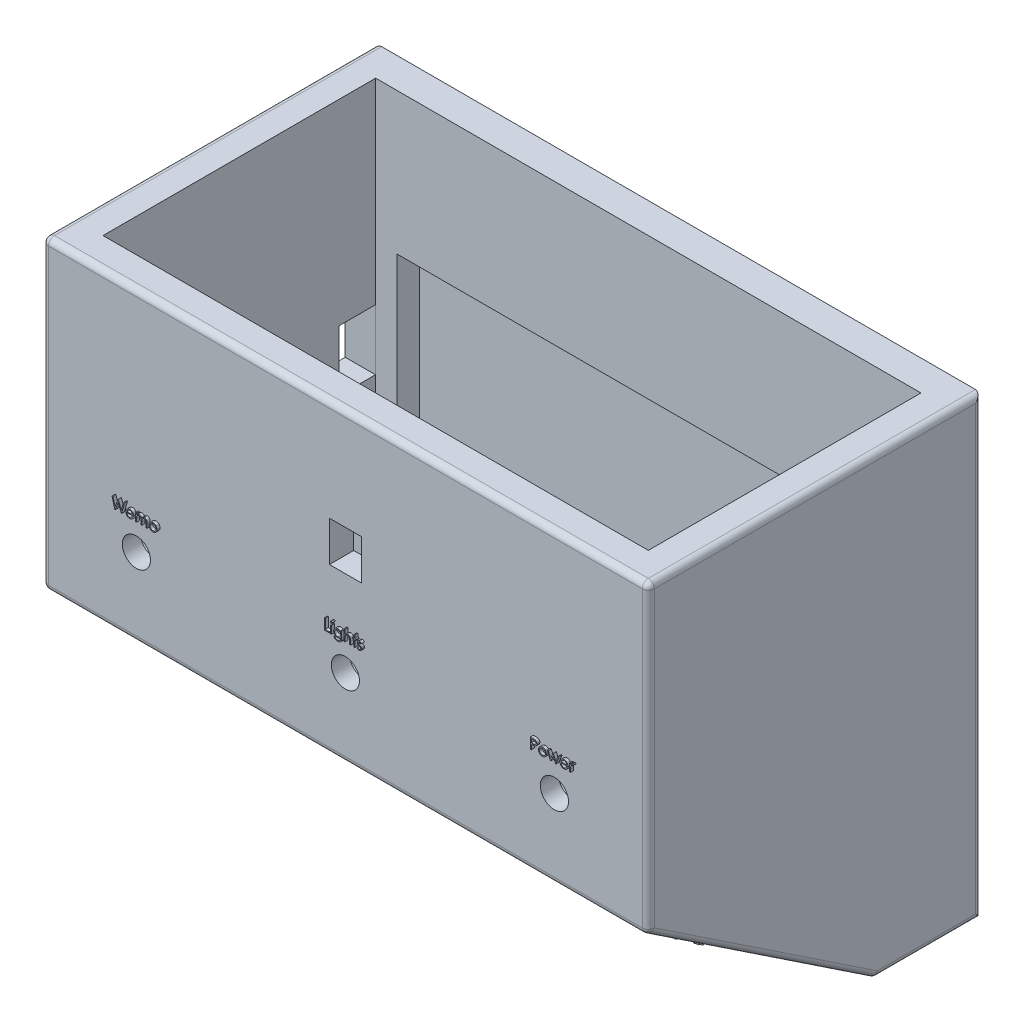
SolidWorks part; units mm, degrees
ref_plane "Front Plane" through (0, 0, 0) normal (0, 0, 1) x (1, 0, 0)
ref_plane "Top Plane" through (0, 0, 0) normal (0, 1, 0) x (1, 0, 0)
ref_plane "Right Plane" through (0, 0, 0) normal (1, 0, 0) x (0, 0, -1)
sketch "Sketch2" plane through (0, 0, 0) normal (0, 0, 1) x (1, 0, 0)
  line L1 (-100, 75) -> (100, 75)
  line L2 (-100, 75) -> (-100, -75)
  line L3 (-100, -75) -> (100, -75)
  line L4 (100, 75) -> (100, -75)
  line L5 (-100, 75) -> (100, -75) construction
  line L6 (-100, -75) -> (100, 75) construction
  point P0 (0, 0)
  dimension "D1" = 150
  dimension "D2" = 200
extrude "Boss-Extrude1" add sketch "Sketch2" along normal blind 35
sketch "Sketch3" plane through (0, 0, 35) normal (0, 0, 1) x (1, 0, 0)
  line L0 (100, -75) -> (100, 75) construction
  line L1 (-100, 75) -> (100, 75)
  line L2 (-100, 75) -> (-100, -25)
  line L3 (-100, -25) -> (100, -25)
  line L4 (100, 75) -> (100, -25)
  dimension "D1" = 100
extrude "Boss-Extrude2" add sketch "Sketch3" along normal blind 75
loft "Loft3" add section face at (0, -50, 35) section face at (0, -25, 72.5) connector at (-100, -75, 35) connector at (-100, -25, 110)
sketch "Sketch6" plane through (0, -68.0769, 45.3846) normal (0, -0.8321, 0.5547) x (1, 0, 0)
  line L1 (-33, 22.408) -> (13, 22.408)
  line L2 (-33, 22.408) -> (-33, 42.908)
  line L3 (-33, 42.908) -> (13, 42.908)
  line L4 (13, 22.408) -> (13, 42.908)
  line L5 (-33, 22.408) -> (13, 42.908) construction
  line L6 (-33, 42.908) -> (13, 22.408) construction
  line L7 (36, 18.658) -> (64, 18.658)
  line L8 (36, 18.658) -> (36, 46.658)
  line L9 (36, 46.658) -> (64, 46.658)
  line L10 (64, 18.658) -> (64, 46.658)
  line L11 (36, 18.658) -> (64, 46.658) construction
  line L12 (36, 46.658) -> (64, 18.658) construction
  line L13 (-100, 77.658) -> (100, 77.658) construction
  line L14 (-81.5, 9.7438) -> (-58.5, 9.7438)
  line L15 (-100, -12.4808) -> (-100, 77.658) construction
  line L16 (-81.5, 9.7438) -> (-81.5, 55.5722)
  line L17 (-81.5, 55.5722) -> (-58.5, 55.5722)
  line L18 (-58.5, 9.7438) -> (-58.5, 55.5722)
  line L19 (-81.5, 9.7438) -> (-58.5, 55.5722) construction
  line L20 (-81.5, 55.5722) -> (-58.5, 9.7438) construction
  line L21 (89.1768, 18.158) -> (73.7768, 18.158)
  line L22 (89.1768, 18.158) -> (89.1768, 46.658)
  line L23 (89.1768, 46.658) -> (73.7768, 46.658)
  line L24 (73.7768, 18.158) -> (73.7768, 46.658)
  line L25 (89.1768, 18.158) -> (73.7768, 46.658) construction
  line L26 (89.1768, 46.658) -> (73.7768, 18.158) construction
  line L27 (73.7768, 38.408) -> (89.1768, 38.408)
  line L28 (73.7768, 38.408) -> (73.7768, 26.408)
  line L29 (73.7768, 26.408) -> (89.1768, 26.408)
  line L30 (89.1768, 38.408) -> (89.1768, 26.408)
  line L31 (73.7768, 38.408) -> (89.1768, 26.408) construction
  line L32 (73.7768, 26.408) -> (89.1768, 38.408) construction
  line L33 (-31.75, 41.408) -> (11.75, 41.408)
  line L34 (-31.75, 41.408) -> (-31.75, 23.908)
  line L35 (-31.75, 23.908) -> (11.75, 23.908)
  line L36 (11.75, 41.408) -> (11.75, 23.908)
  line L37 (-31.75, 41.408) -> (11.75, 23.908) construction
  line L38 (-31.75, 23.908) -> (11.75, 41.408) construction
  line L39 (36, 39.066) -> (64, 39.066)
  line L40 (36, 39.066) -> (36, 18.658)
  line L41 (36, 18.658) -> (64, 18.658)
  line L42 (64, 39.066) -> (64, 18.658)
  line L43 (-15.5, 42.908) -> (-4.5, 42.908)
  line L44 (-15.5, 42.908) -> (-15.5, 41.408)
  line L45 (-15.5, 41.408) -> (-4.5, 41.408)
  line L46 (-4.5, 42.908) -> (-4.5, 41.408)
  circle A0 centre (-70, 32.658) radius 18.5
  circle A1 centre (-70, 32.658) radius 11.25
  point P2 (-10, 32.658)
  point P7 (50, 32.658)
  point P21 (81.4768, 32.408)
  point P22 (81.4768, 32.408)
  point P31 (-10, 32.658)
  dimension "D1" = 37
  dimension "D12" = 22.5
  dimension "D2" = 20.5
  dimension "D3" = 46
  dimension "D4" = 45
  dimension "D5" = 45
  dimension "D6" = 45
  dimension "D7" = 30
  dimension "D8" = 60
  dimension "D9" = 60
  dimension "D10" = 28
  dimension "D11" = 28
  dimension "D13" = 23
  dimension "D14" = 28.5
  dimension "D15" = 15.4
  dimension "D16" = 12
  dimension "D17" = 43.5
  dimension "D18" = 17.5
  dimension "D19" = 11
  dimension "D20" = 16.25
sketch "Sketch8" plane through (0, -68.0769, 45.3846) normal (0, -0.8321, 0.5547) x (1, 0, 0)
  line L1 (-100, 77.658) -> (100, 77.658)
  line L2 (-100, 77.658) -> (-100, -12.4808)
  line L3 (-100, -12.4808) -> (100, -12.4808)
  line L4 (100, 77.658) -> (100, -12.4808)
sketch "Sketch9" plane through (0, 75, 0) normal (0, 1, 0) x (1, 0, 0)
  line L1 (-100, 0) -> (100, 0)
  line L2 (-100, 0) -> (-100, -110)
  line L3 (-100, -110) -> (100, -110)
  line L4 (100, 0) -> (100, -110)
shell "Shell2" thickness 10 removed face at (0, 75, 55)
sketch "Sketch26" plane through (0, -75, 0) normal (0, -1, 0) x (1, 0, 0)
  line L0 (0, 0) -> (0, 35) construction
  line L1 (-100, 35) -> (100, 35) construction
  line L3 (14.25, 2) -> (-14.25, 2)
  line L4 (14.25, 2) -> (14.25, 33)
  line L5 (14.25, 33) -> (-14.25, 33)
  line L6 (-14.25, 2) -> (-14.25, 33)
  line L7 (14.25, 2) -> (-14.25, 33) construction
  line L8 (14.25, 33) -> (-14.25, 2) construction
  point P5 (0, 17.5)
  dimension "D1" = 31
  dimension "D2" = 28.5
extrude "Cut-Extrude12" cut sketch "Sketch26" against normal blind 15
sketch "Sketch28" plane through (0, -75, 0) normal (0, -1, 0) x (1, 0, 0)
  line L0 (14.25, 2) -> (14.25, 33) construction
  line L1 (14.25, 33) -> (-14.25, 33) construction
  ellipse E0 centre (14.25, 17.25) end of major axis (6.15, 17.25) minor radius 7
  ellipse E1 centre (-14.25, 17.25) end of major axis (-22.35, 17.25) minor radius 7
  dimension "D1" = 7
  dimension "D2" = 8.75
  dimension "D3" = 8.1
  dimension "D4" = 2
extrude "Cut-Extrude13" cut sketch "Sketch28" against normal blind 9
sketch "Sketch29" plane through (0, -60, 0) normal (0, -1, 0) x (1, 0, 0)
  line L0 (-14.25, 10) -> (14.25, 10) construction
  circle A0 centre (0, 10) radius 5
  dimension "D1" = 10
extrude "Cut-Extrude14" cut sketch "Sketch29" against normal blind 7.5
fillet "Fillet1" radius 2 2 edges at (0, -52.5, 10) (0, -60, 5)
fillet "Fillet2" radius 2 12 edges at (100, -75, 17.5) (100, -50, 72.5) (100, 75, 55) (100, 0, 0) (-100, 0, 0) (-100, 75, 55) (-100, -50, 72.5) (-100, -75, 17.5) (0, 75, 110) (100, 25, 110) (0, -25, 110) (-100, 25, 110)
fillet "Fillet3" radius 2 3 edges at (-99.4142, -74.4142, 34.8226) (99.4142, -74.4142, 34.8226) (0, -75, 35)
sketch "Sketch30" plane through (0, -66, 0) normal (0, -1, 0) x (1, 0, 0)
  line L0 (14.25, 17.25) -> (22.35, 17.25) construction
  line L1 (14.25, 24.25) -> (14.25, 10.25) construction
  line L2 (14.25, 10.25) -> (14.25, 24.25) construction
  line L7 (22.35, 17.25) -> (-22.35, 17.25) construction
  line L8 (0, 17.25) -> (0, 25.5372) construction
  line L9 (-19.35, 17.25) -> (-19.35, 20.6868) construction
  circle A0 centre (19.35, 17.25) radius 1.05
  circle A1 centre (-19.35, 17.25) radius 1.05
  ellipse E0 centre (14.25, 17.25) end of major axis (6.15, 17.25) minor radius 7 (14.25, 10.25) -> (14.25, 24.25) ccw construction
  ellipse E1 centre (14.25, 17.25) end of major axis (6.15, 17.25) minor radius 7 (14.25, 10.25) -> (14.25, 24.25) ccw construction
  ellipse E2 centre (-14.25, 17.25) end of major axis (-22.35, 17.25) minor radius 7 (-14.25, 24.25) -> (-14.25, 10.25) ccw construction
  dimension "D1" = 2.1
  dimension "D2" = 3
  dimension "D3" = 3
  dimension "D4" = 2
extrude "Cut-Extrude16" cut sketch "Sketch30" against normal blind 10
sketch "Sketch34" plane through (0, 0, 110) normal (0, 0, 1) x (1, 0, 0)
  line L0 (0, 0) -> (-98, 0) construction
  line L1 (-98, 73) -> (-98, -23.9296) construction
  line L2 (0, 0) -> (0, 73) construction
  line L3 (98, 73) -> (-98, 73) construction
  circle A0 centre (-69, 0) radius 4.65
  circle A1 centre (-69, 0) radius 3.5
  circle A2 centre (0, 0) radius 4.65
  circle A3 centre (0, 0) radius 3.5
  circle A4 centre (69, 0) radius 4.65
  circle A5 centre (69, 0) radius 3.5
  dimension "D1" = 9.3
  dimension "D2" = 7
  dimension "D3" = 29
  dimension "D4" = 3
extrude "Cut-Extrude18" cut sketch "Sketch34" against normal blind 15 contours A3 | A5 | A1
extrude "Cut-Extrude19" cut sketch "Sketch34<3>" against normal blind 6
sketch "Sketch34<3>" plane through (0, 0, 110) normal (0, 0, 1) x (1, 0, 0) same geometry as "Sketch34"
fillet "Fillet4" radius 2 3 edges at (-65.5, 0, 104) (3.5, 0, 104) (72.5, 0, 104)
sketch "Sketch35" plane through (0, 0, 10) normal (0, 0, 1) x (1, 0, 0)
  line L1 (83, -28.25) -> (-83, -28.25)
  line L2 (83, -28.25) -> (83, 28.25)
  line L3 (83, 28.25) -> (-83, 28.25)
  line L4 (-83, -28.25) -> (-83, 28.25)
  line L5 (83, -28.25) -> (-83, 28.25) construction
  line L6 (83, 28.25) -> (-83, -28.25) construction
  point P0 (0, 0)
  dimension "D1" = 56.5
  dimension "D2" = 166
extrude "Cut-Extrude20" cut sketch "Sketch35" against normal blind 7.5
sketch "Sketch38" plane through (0, -68.0769, 45.3846) normal (0, -0.8321, 0.5547) x (1, 0, 0)
  text T0 "           Volume/\r\nChange Playlist" font "Century Gothic" height 3.5
extrude "Boss-Extrude8" add sketch "Sketch38" along normal blind 1
sketch "Sketch39" plane through (0, 0, 110) normal (0, 0, 1) x (1, 0, 0)
  line L0 (0, 0) -> (0, 9.7465) construction
  line L1 (0, 9.7465) -> (75.4341, 9.7465) construction
  line L2 (75.4341, 9.7465) -> (-74.7186, 9.7465) construction
sketch "Sketch42" plane through (0, 0, 2.5) normal (0, 0, 1) x (1, 0, 0)
  line L0 (69.0994, 0) -> (69.0994, 9.7465) construction
  line L1 (-69.0387, 0) -> (-69.0387, 17.9151) construction
  line L2 (0, 9.7465) -> (75.4341, 9.7465) construction
  text T0 "Power"
  text T1 "Lights"
  text T2 "Wemo"
  point P2 (0, 0)
  point P5 (0, 0)
  point P6 (69.0994, 9.7465)
extrude "Boss-Extrude10" add sketch "Sketch42" along normal blind 1 from surface starting at face at (-64.35, 0, 110)
extrude "Cut-Extrude23" cut sketch "Sketch6" against normal blind 15 contours L36 L33 L34 L35 | L18 A0 | L16 A0 | L8 L39 L10 L9 | L29 L24 L21 L22 | L24 L27 L22 L23 region at (-10, -49.9615, 72.5577) region at (50, -44.3013, 81.048) region at (-84.351, -49.9615, 72.5577) region at (-55.649, -49.9615, 72.5577) region at (81.4768, -55.7165, 63.9252) region at (81.4768, -44.4838, 80.7742)
ref_plane "Plane7" through (-31.75, -54.8151, 65.2773) normal (1, 0, 0) x (0, 0, -1)
extrude "Cut-Extrude25" cut sketch "Sketch6<6>" against normal blind 8 contours L1 L4 L3 L2 L33 L36 L35 L34 region at (-32.4964, -49.9615, 72.5577)
sketch "Sketch6<6>" plane through (0, -68.0769, 45.3846) normal (0, -0.8321, 0.5547) x (1, 0, 0) same geometry as "Sketch6"
extrude "Cut-Extrude26" cut sketch "Sketch6<7>" against normal blind 5 contours L18 A0 L16 A1 region at (-81.4564, -49.9615, 72.5577)
sketch "Sketch6<7>" plane through (0, -68.0769, 45.3846) normal (0, -0.8321, 0.5547) x (1, 0, 0) same geometry as "Sketch6"
extrude "Cut-Extrude27" cut sketch "Sketch6<8>" against normal blind 7 contours L39 L8 L7 L10 region at (50, -52.0671, 69.3993)
sketch "Sketch6<8>" plane through (0, -68.0769, 45.3846) normal (0, -0.8321, 0.5547) x (1, 0, 0) same geometry as "Sketch6"
extrude "Cut-Extrude28" cut sketch "Sketch6<9>" against normal blind 7 contours L24 L29 L22 L27 region at (81.4768, -50.1002, 72.3497)
sketch "Sketch6<9>" plane through (0, -68.0769, 45.3846) normal (0, -0.8321, 0.5547) x (1, 0, 0) same geometry as "Sketch6"
extrude "Cut-Extrude29" cut sketch "Sketch6<10>" against normal blind 15 contours L46 L3 L44 L33 region at (-10, -44.6919, 80.4622)
sketch "Sketch6<10>" plane through (0, -68.0769, 45.3846) normal (0, -0.8321, 0.5547) x (1, 0, 0) same geometry as "Sketch6"
sketch "Sketch46" plane through (0, 0, 110) normal (0, 0, 1) x (1, 0, 0)
  line L0 (0, -25.5937) -> (0, 55.0917) construction
  line L1 (98, -25.5937) -> (-98, -25.5937) construction
  line L2 (0, 55.0917) -> (-98, 55.0917) construction
  line L3 (-98, 73) -> (-98, -23.9296) construction
  line L5 (-5.25, 41.584) -> (5.25, 41.584)
  line L6 (-5.25, 41.584) -> (-5.25, 28.334)
  line L7 (-5.25, 28.334) -> (5.25, 28.334)
  line L8 (5.25, 41.584) -> (5.25, 28.334)
  line L9 (-5.25, 41.584) -> (5.25, 28.334) construction
  line L10 (-5.25, 28.334) -> (5.25, 41.584) construction
  line L11 (-5.25, 37.834) -> (5.25, 37.834)
  line L12 (-5.25, 37.834) -> (-5.25, 41.584)
  line L13 (-5.25, 41.584) -> (5.25, 41.584)
  line L14 (5.25, 37.834) -> (5.25, 41.584)
  point P5 (0, 34.959)
  dimension "D1" = 10.5
  dimension "D2" = 13.25
  dimension "D3" = 3.75
extrude "Cut-Extrude31" cut sketch "Sketch46" against normal blind 8 contours L11 L6 L7 L8 region at (0, 33.084, 110)
extrude "Cut-Extrude32" cut sketch "Sketch46<5>" against normal blind 15 contours L6 L11 L8 L5 region at (0, 39.709, 110)
sketch "Sketch46<5>" plane through (0, 0, 110) normal (0, 0, 1) x (1, 0, 0) same geometry as "Sketch46"
sketch "Sketch47" plane through (-90, 0, 0) normal (1, 0, 0) x (0, 0, -1)
  line L1 (-7.4842, -28.245) -> (-7.7836, 28.1387) construction
  line L2 (-10.0696, 10.25) -> (-22.0696, 10.25)
  line L3 (-10.0696, 10.25) -> (-10.0696, -9.75)
  line L4 (-10.0696, -9.75) -> (-22.0696, -9.75)
  line L5 (-22.0696, 10.25) -> (-22.0696, -9.75)
  line L6 (-10.0696, 10.25) -> (-22.0696, -9.75) construction
  line L7 (-10.0696, -9.75) -> (-22.0696, 10.25) construction
  line L9 (0, 0) -> (-35.4522, 0) construction
  line L10 (-2.5, -28.25) -> (-10, -28.25) construction
  point P2 (-16.0696, 0.25)
  dimension "D1" = 12
  dimension "D2" = 20
  dimension "D3" = 28.5
extrude "Cut-Extrude33" cut sketch "Sketch47" against normal blind 15
sketch "Sketch5" plane through (0, -72.7941, 121.3235) normal (0, -0.5145, 0.8575) x (1, 0, 0)
  line L1 (-250, 55.737) -> (250, 55.737)
  line L2 (-250, 55.737) -> (-250, -90.0368)
  line L3 (-250, -90.0368) -> (250, -90.0368)
  line L4 (250, 55.737) -> (250, -90.0368)
  line L5 (136, -14.25) -> (164, -14.25)
  line L6 (136, -14.25) -> (136, 14.25)
  line L7 (136, 14.25) -> (164, 14.25)
  line L8 (164, -14.25) -> (164, 14.25)
  line L9 (136, -14.25) -> (164, 14.25) construction
  line L10 (136, 14.25) -> (164, -14.25) construction
  line L11 (23, -10.5) -> (-23, -10.5)
  line L12 (23, -10.5) -> (23, 10.5)
  line L13 (23, 10.5) -> (-23, 10.5)
  line L14 (-23, -10.5) -> (-23, 10.5)
  line L15 (23, -10.5) -> (-23, 10.5) construction
  line L16 (23, 10.5) -> (-23, -10.5) construction
  circle A0 centre (-150, 0) radius 18.5
  point P8 (150, 0)
  point P9 (-250, -17.1499)
  point P16 (0, 0)
  dimension "D1" = 37
  dimension "D2" = 100
  dimension "D4" = 28
  dimension "D5" = 28.5
  dimension "D6" = 100
  dimension "D7" = 21
  dimension "D8" = 46
